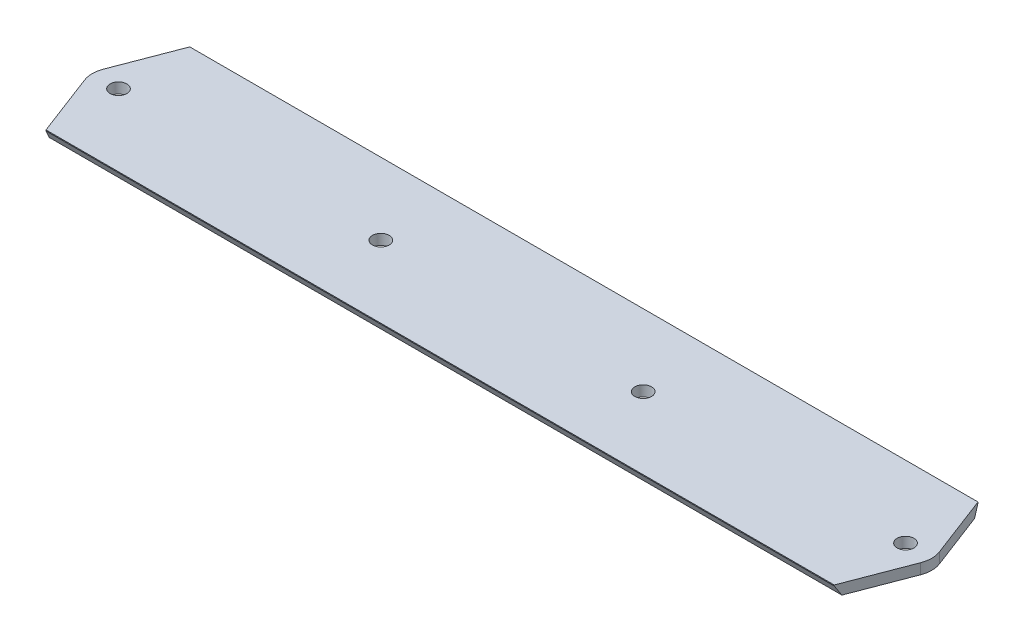
SolidWorks part; units mm, degrees
material "Медь"
ref_plane "Front" through (0, 0, 0) normal (0, 0, 1) x (1, 0, 0)
ref_plane "Top" through (0, 0, 0) normal (0, 1, 0) x (1, 0, 0)
ref_plane "Right" through (0, 0, 0) normal (1, 0, 0) x (0, 0, -1)
sketch "Эскиз1" plane through (0, 0, 0) normal (0, 1, 0) x (1, 0, 0)
  line L0 (-75, 14) -> (-79.6702, 1.7857)
  line L1 (75, -14) -> (-75, -14)
  line L2 (75, -14) -> (75, -1.6)
  line L3 (75, 14) -> (-75, 14)
  line L4 (-75, -14) -> (-75, -1.6)
  line L5 (75, -14) -> (-75, 14) construction
  line L6 (75, 14) -> (-75, -14) construction
  line L7 (-75, -14) -> (-79.6702, -1.7857)
  line L8 (-75, 1.6) -> (-75, 14)
  line L9 (0, 0) -> (0, 14) construction
  line L10 (75, -14) -> (79.6702, -1.7857)
  line L11 (75, 14) -> (79.6702, 1.7857)
  line L12 (75, 1.6) -> (75, 14)
  circle A0 centre (-75, 0) radius 1.6
  arc A1 (-79.6702, 1.7857) -> (-79.6702, -1.7857) centre (-75, 0) ccw
  circle A2 centre (75, 0) radius 1.6
  arc A3 (79.6702, 1.7857) -> (79.6702, -1.7857) centre (75, 0) cw
  circle A4 centre (-25, 0) radius 1.6
  circle A5 centre (25, 0) radius 1.6
  point P0 (0, 0)
  dimension "D3" = 3.2
  dimension "D4" = 10
  dimension "D6" = 50
  dimension "D1" = 150
  dimension "D2" = 28
  dimension "D7" = 50
  dimension "D5" = 3
extrude "Бобышка-Вытянуть1" add sketch "Эскиз1" along normal blind 2 contours L2 A2 L12 L3 L8 A0 L4 L1 A5 A4 | A3 L11 L12 A2 L2 L10 | L0 A1 L7 L4 A0 L8 region at (-76.8274, 0, 0) region at (0, 0, 0) region at (76.8274, 0, 0)
ref_plane "Плоскость1" through (-80, 0, 0) normal (-1, 0, 0) x (0, 0, 1)
sketch "Эскиз3" plane through (-80, 0, 0) normal (-1, 0, 0) x (0, 0, 1)
  line L0 (-12.6453, 0) -> (-14, 0)
  line L1 (-14, 0) -> (14, 0) construction
  line L2 (-14, 0) -> (-14, 2)
  line L3 (-14, 2) -> (14, 2) construction
  line L4 (14, 0) -> (14, 2)
  line L5 (-14, 0) -> (14, 2) construction
  line L6 (-14, 2) -> (14, 0) construction
  line L7 (-14, 2) -> (-13.8, 2)
  line L8 (-13.8, 2) -> (-12.6453, 0)
  line L9 (0, 2) -> (0, 0) construction
  line L10 (14, 2) -> (13.8, 2)
  line L11 (13.8, 2) -> (12.6453, 0)
  line L12 (12.6453, 0) -> (14, 0)
  line L13 (14, 0) -> (14, 2) construction
  point P4 (0, 1)
  dimension "D1" = 0.2
  dimension "D2" = 120
extrude "Вырез-Вытянуть1" cut sketch "Эскиз3" against normal through all
chamfer "Фаска1" distance 0.2 angle 30 1 edges at (0, 2, -13.8) first distance on face at (0, 1, -13.2226)
chamfer "Фаска2" distance 0.2 angle 30 1 edges at (0, 2, 13.8) first distance on face at (0, 1, 13.2226)
